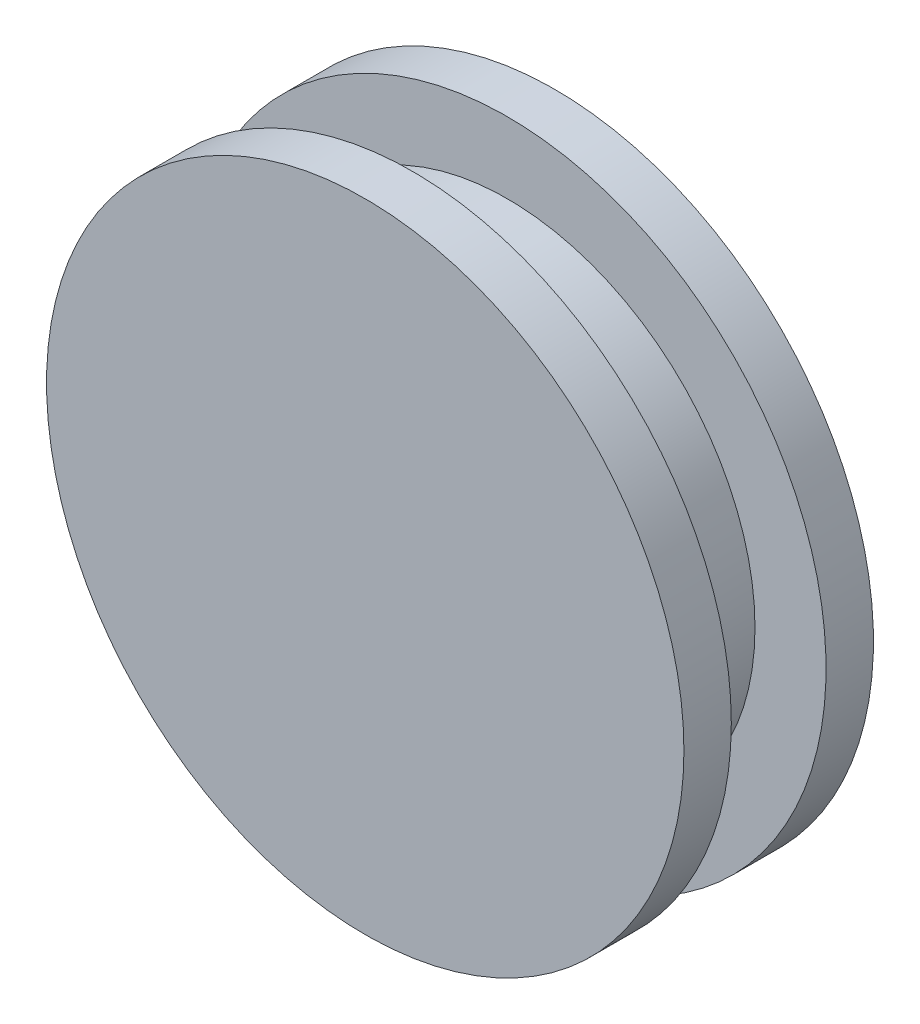
SolidWorks part; units mm, degrees
ref_plane "前视基准面" through (0, 0, 0) normal (0, 0, 1) x (1, 0, 0)
ref_plane "上视基准面" through (0, 0, 0) normal (0, 1, 0) x (1, 0, 0)
ref_plane "右视基准面" through (0, 0, 0) normal (1, 0, 0) x (0, 0, -1)
sketch "草图1" plane through (0, 0, 0) normal (0, 0, 1) x (1, 0, 0)
  circle A0 centre (0, 0) radius 4.375
  circle A1 centre (0, 0) radius 5.2262
extrude "凸台-拉伸1" add sketch "草图1" along normal blind 4
ref_axis "基准轴1" through (0, 0, 4) along (0, 0, -1)
sketch "草图2" plane through (0, 0, 0) normal (0, 0, 1) x (1, 0, 0)
  line L0 (0, 0) -> (0, 3.5238) construction
  arc A0 (0.3161, 3.5096) -> (-0.3161, 3.5096) centre (0, 0) ccw
  arc A1 (1.0078, 4.4442) -> (-1.0078, 4.4442) centre (0, 0) ccw
  spline S0 degree 3 poles (0.3161, 3.5096) (0.3175, 3.5211) (0.3204, 3.5358) (0.3249, 3.5543) (0.328, 3.5659) (0.3317, 3.5788) (0.3361, 3.5929) (0.3412, 3.6083) (0.3471, 3.6249) (0.3538, 3.6427) (0.3614, 3.6617) (0.3699, 3.6818) (0.3794, 3.703) (0.3899, 3.7254) (0.4015, 3.7487) (0.4142, 3.7731) (0.428, 3.7985) (0.4431, 3.8248) (0.4594, 3.852) (0.477, 3.88) (0.4959, 3.9089) (0.5162, 3.9386) (0.5379, 3.969) (0.5611, 4.0001) (0.5857, 4.0318) (0.6118, 4.0642) (0.6395, 4.097) (0.6688, 4.1304) (0.6997, 4.1643) (0.7322, 4.1985) (0.7664, 4.2331) (0.8023, 4.2679) (0.84, 4.303) (0.8793, 4.3383) (0.9349, 4.3861) (0.9781, 4.4212) (1.0078, 4.4442) knots 0 0 0 0 0.029141 0.038065 0.048178 0.059481 0.071973 0.085656 0.100528 0.11659 0.133842 0.152283 0.171915 0.192736 0.214747 0.237947 0.262338 0.287918 0.314688 0.342648 0.371797 0.402137 0.433666 0.466385 0.500293 0.535392 0.57168 0.609158 0.647826 0.687683 0.728731 0.770968 0.814395 0.859011 0.904818 1 1 1 1
  spline S1 degree 3 poles (-0.3161, 3.5096) (-0.3175, 3.5211) (-0.3204, 3.5358) (-0.3249, 3.5543) (-0.328, 3.5659) (-0.3317, 3.5788) (-0.3361, 3.5929) (-0.3412, 3.6083) (-0.3471, 3.6249) (-0.3538, 3.6427) (-0.3614, 3.6617) (-0.3699, 3.6818) (-0.3794, 3.703) (-0.3899, 3.7254) (-0.4015, 3.7487) (-0.4142, 3.7731) (-0.428, 3.7985) (-0.4431, 3.8248) (-0.4594, 3.852) (-0.477, 3.88) (-0.4959, 3.9089) (-0.5162, 3.9386) (-0.5379, 3.969) (-0.5611, 4.0001) (-0.5857, 4.0318) (-0.6118, 4.0642) (-0.6395, 4.097) (-0.6688, 4.1304) (-0.6997, 4.1643) (-0.7322, 4.1985) (-0.7664, 4.2331) (-0.8023, 4.2679) (-0.84, 4.303) (-0.8793, 4.3383) (-0.9349, 4.3861) (-0.9781, 4.4212) (-1.0078, 4.4442) knots 0 0 0 0 0.029141 0.038065 0.048178 0.059481 0.071973 0.085656 0.100528 0.11659 0.133842 0.152283 0.171915 0.192736 0.214747 0.237947 0.262338 0.287918 0.314688 0.342648 0.371797 0.402137 0.433666 0.466385 0.500293 0.535392 0.57168 0.609158 0.647826 0.687683 0.728731 0.770968 0.814395 0.859011 0.904818 1 1 1 1
extrude "凸台-拉伸2" add sketch "草图2" along normal blind 4
pattern_circular "阵列(圆周)1" count 15 every 24 about axis through (0, 0, 4) along (0, 0, -1) of "凸台-拉伸2"
sketch "草图3" plane through (0, 0, 0) normal (0, 0, 1) x (1, 0, 0)
  circle A0 centre (0, 0) radius 3.75 construction
  dimension "Dn" = 7.5
sketch "草图6" plane through (0, 0, 4) normal (0, 0, 1) x (1, 0, 0)
  circle A0 centre (0, 0) radius 6.7262
  circle A1 centre (0, 0) radius 5.2262 construction
  dimension "D1" = 1.5
extrude "凸台-拉伸3" add sketch "草图6" against normal blind 1
sketch "草图7" plane through (0, 0, 0) normal (0, 0, -1) x (-1, 0, 0)
  circle A0 centre (0, 0) radius 6.7262
  circle A1 centre (0, 0) radius 6.7262 construction
extrude "凸台-拉伸4" add sketch "草图7" against normal blind 1
